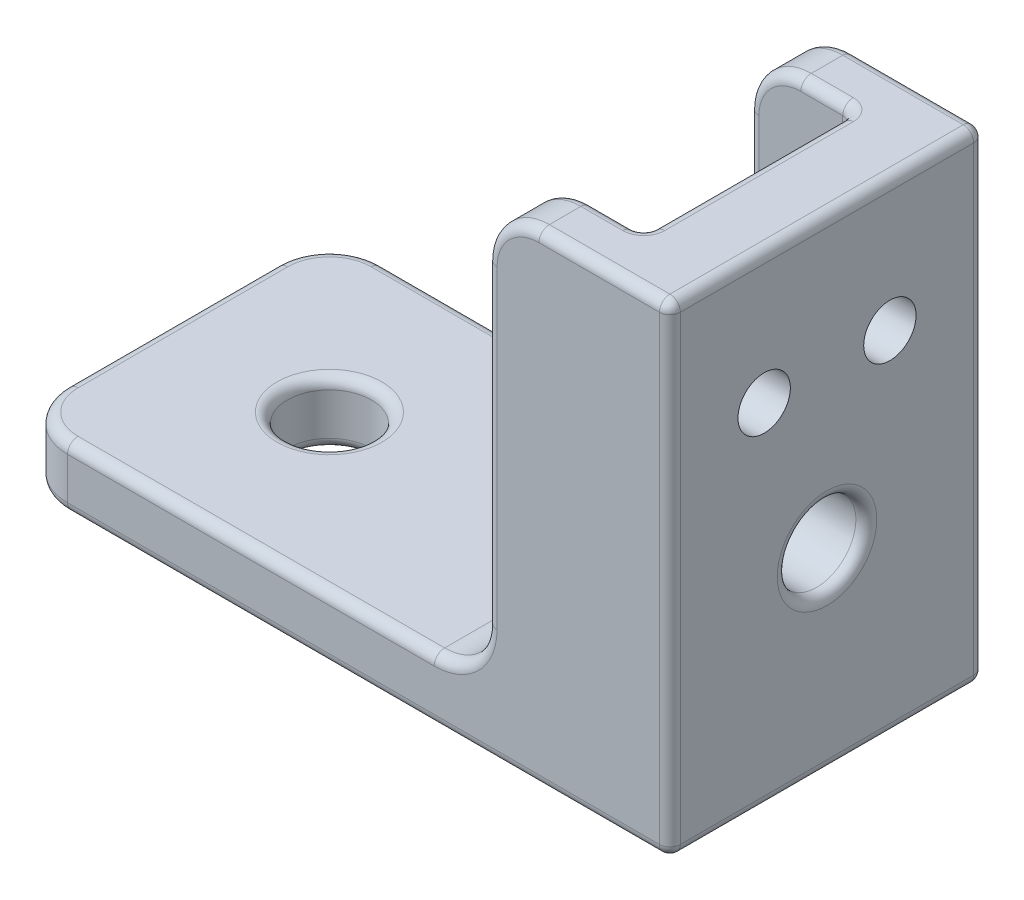
SolidWorks part; units mm, degrees
ref_plane "Front Plane" through (0, 0, 0) normal (0, 0, 1) x (1, 0, 0)
ref_plane "Top Plane" through (0, 0, 0) normal (0, 1, 0) x (1, 0, 0)
ref_plane "Right Plane" through (0, 0, 0) normal (1, 0, 0) x (0, 0, -1)
sketch "Sketch1" plane through (0, 0, 0) normal (0, 1, 0) x (1, 0, 0)
  line L1 (0, 0) -> (25, 0)
  line L2 (0, 0) -> (0, -12)
  line L3 (0, -12) -> (25, -12)
  line L4 (25, 0) -> (25, -12)
  circle A0 centre (6, -6) radius 1.6
  dimension "D4" = 3.2
  dimension "D1" = 12
  dimension "D2" = 25
  dimension "D3" = 6
  dimension "D5" = 6
extrude "Boss-Extrude1" add sketch "Sketch1" along normal blind 2.4
sketch "Sketch3" plane through (0, 2.4, 0) normal (0, 1, 0) x (1, 0, 0)
  line L0 (25, 0) -> (0, 0) construction
  line L1 (25, -12) -> (22, -12)
  line L2 (25, -12) -> (25, 0)
  line L3 (25, 0) -> (22, 0)
  line L4 (22, -12) -> (22, 0)
  line L6 (22, 0) -> (18, 0)
  line L7 (22, 0) -> (22, -2)
  line L8 (22, -2) -> (18, -2)
  line L9 (18, 0) -> (18, -2)
  line L10 (22, -12) -> (18, -12)
  line L11 (22, -12) -> (22, -10)
  line L12 (22, -10) -> (18, -10)
  line L13 (18, -12) -> (18, -10)
  line M7 (0, -12) -> (25, -12)
  line M8 (25, -12) -> (25, 0)
  line M9 (25, 0) -> (0, 0)
  dimension "D1" = 3
  dimension "D2" = 2
  dimension "D3" = 2
  dimension "D4" = 4
  dimension "D5" = 4
extrude "Boss-Extrude2" add sketch "Sketch3" along normal blind 16 contours L9 L8 L4 M9 | L4 M7 M8 M9 | L13 L4 L12 M7 region at (23.5, 2.4, 6) region at (20, 2.4, 11) region at (20, 2.4, 1)
sketch "Sketch4" plane through (22, 0, 0) normal (-1, 0, 0) x (0, 0, 1)
  line L0 (10, 2.4) -> (2, 2.4) construction
  line L1 (0, 18.4) -> (0, 2.4) construction
  line L2 (10, 18.4) -> (2, 18.4) construction
  line L3 (2, 18.4) -> (2, 2.4) construction
  line L4 (10, 18.4) -> (10, 2.4) construction
  circle A0 centre (6, 7.4) radius 1.5
  circle A1 centre (3.6, 13.4) radius 1
  circle A2 centre (8.4, 13.4) radius 1
  dimension "D3" = 6
  dimension "D1" = 3
  dimension "D4" = 2
  dimension "D5" = 2
  dimension "D2" = 5
  dimension "D6" = 5
  dimension "D7" = 5
  dimension "D8" = 1.6
  dimension "D9" = 1.6
extrude "Cut-Extrude1" cut sketch "Sketch4" against normal blind 11.6
fillet "Fillet1" radius 2 6 edges at (18, 2.4, 11) (18, 2.4, 1) (18, 18.4, 1) (18, 18.4, 11) (0, 1.2, 0) (0, 1.2, 12)
fillet "Fillet2" radius 0.4 18 edges at (22.5, 18.4, 0) (18.5858, 17.8142, 0) (18, 10.4, 0) (17.4142, 2.9858, 0) (22.5, 18.4, 12) (18.5858, 17.8142, 12) (18, 10.4, 12) (17.4142, 2.9858, 12) (0.5858, 2.4, 11.4142) (0, 2.4, 6) (0.5858, 2.4, 0.5858) (9, 2.4, 0) (19, 2.4, 2) (22, 2.4, 6) (19, 2.4, 10) (9, 2.4, 12) (6, 2.4, 7.6) (25, 7.4, 7.5)
fillet "Fillet3" radius 0.4 5 edges at (21.8828, 2.5172, 9.8828) (21.8828, 2.5172, 2.1172) (22, 7.4, 7.5) (22, 10.6, 10) (22, 10.6, 2)
fillet "Fillet4" radius 0.4 2 edges at (22, 13.4, 9.4) (22, 13.4, 4.6)
fillet "Fillet5" radius 0.4 12 edges at (25, 9, 12) (25, 18.2828, 11.8828) (25, 18.4, 6) (25, 18.2828, 0.1172) (13.5, 0, 12) (0.5858, 0, 11.4142) (0, 0, 6) (0.5858, 0, 0.5858) (25, 0, 6) (25, 9, 0) (6, 0, 7.6) (13.5, 0, 0)
fillet "Fillet6" radius 0.4 13 edges at (16.8833, 2.6056, 9.9496) (17.7889, 3.5056, 10) (18, 10.4, 10) (18.5858, 17.8142, 10) (20.8, 18.4, 10) (21.8828, 18.4, 9.8828) (16.8833, 2.6056, 2.0504) (17.7889, 3.5056, 2) (18, 10.4, 2) (18.5858, 17.8142, 2) (20.8, 18.4, 2) (21.8828, 18.4, 2.1172) (22, 18.4, 6)
equation "\"D3@Sketch1\"=\"D1@Sketch1\"/2"
equation "\"D3@Sketch4\"=\"D1@Sketch1\"/2"
equation "\"D9@Sketch4\"=\"D8@Sketch4\""
equation "\"D7@Sketch4\"=\"D6@Sketch4\""
